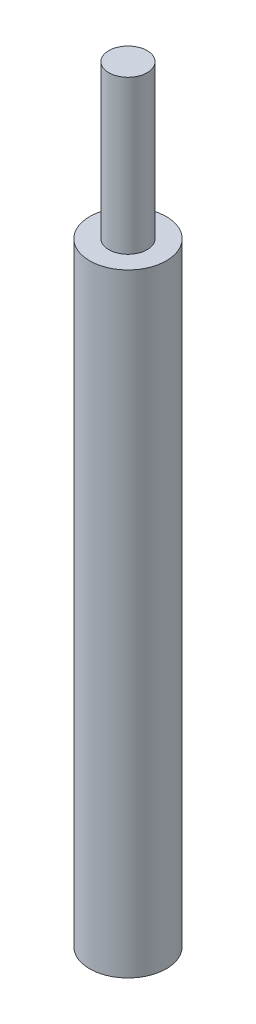
SolidWorks part; units mm, degrees
ref_plane "Front Plane" through (0, 0, 0) normal (0, 0, 1) x (1, 0, 0)
ref_plane "Top Plane" through (0, 0, 0) normal (0, 1, 0) x (1, 0, 0)
ref_plane "Right Plane" through (0, 0, 0) normal (1, 0, 0) x (0, 0, -1)
sketch "Sketch1" plane through (0, 0, 0) normal (0, 1, 0) x (1, 0, 0)
  circle A0 centre (0, 0) radius 3.175
  dimension "D1" = 6.35
extrude "Boss-Extrude1" add sketch "Sketch1" along normal blind 50.8
sketch "Sketch2" plane through (0, 50.8, 0) normal (0, 1, 0) x (1, 0, 0)
  circle A0 centre (0, 0) radius 1.5875
  dimension "D1" = 3.175
extrude "Boss-Extrude2" add sketch "Sketch2" along normal blind 12.7 contours A0
sketch "Sketch4" plane through (0, 0, 0) normal (0, -1, 0) x (1, 0, 0)
  line L0 (-3.175, 0) -> (3.175, 0) construction
  line L1 (0, 3.175) -> (0, -3.175) construction
  circle A0 centre (0, 0) radius 3.175 construction
  point P9 (0, 0)
hole_wizard "1/8 (0.125) Diameter Hole1" positions "Sketch4" profile "Sketch5" hole size "1/8" standard "ANSI Inch"
sketch "Sketch5" plane through (0, 0, 0) normal (1, 0, 0) x (0, 0, -1)
  line L0 (0, 0) -> (0, 13.6539)
  line L1 (0, 13.6539) -> (1.5875, 12.7)
  line L2 (1.5875, 12.7) -> (1.5875, 0)
  line L5 (1.5875, 0) -> (0, 0)
  line L10 (0, 13.6539) -> (-1.5875, 12.7) construction
  line L11 (0, -6.35) -> (0, 107.95) construction
  dimension "Hole Dia." = 3.175
  dimension "Hole Depth" = 12.7
  dimension "Drill Angle" = 118
